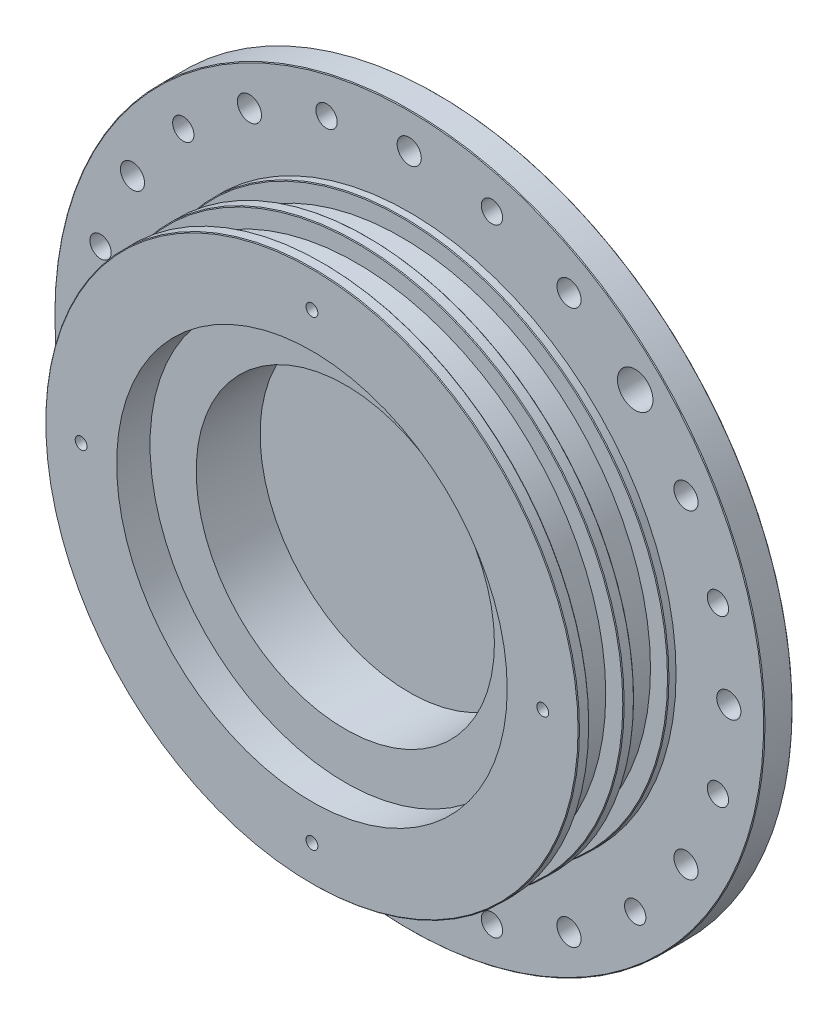
SolidWorks part; units mm, degrees
other "Marquage1"
sketch "Esquisse22" plane through (-100, 100, -114.225) normal (-0.6969, 0.6451, 0.3132) x (0.5706, 0.7634, -0.3027)
sketch "Esquisse26" plane through (-110, 110, -114.225) normal (-0.6969, 0.6451, 0.3132) x (0.5706, 0.7634, -0.3027)
sketch "Esquisse28" plane through (-110, 110, -114.225) normal (-0.6969, 0.6451, 0.3132) x (0.5706, 0.7634, -0.3027)
sketch "Esquisse31" plane through (-110, 110, -114.225) normal (-0.6969, 0.6451, 0.3132) x (0.5706, 0.7634, -0.3027)
sketch "Esquisse32" plane through (-100, 100, -114.225) normal (-0.6969, 0.6451, 0.3132) x (0.5706, 0.7634, -0.3027)
material "AISI 316 Barre d'acier inoxydable recuit (SS)"
ref_plane "Plan de face" through (0, 0, 0) normal (0, 0, 1) x (1, 0, 0)
ref_plane "Plan de dessus" through (0, 0, 0) normal (0, 1, 0) x (1, 0, 0)
ref_plane "Plan de droite" through (0, 0, 0) normal (1, 0, 0) x (0, 0, -1)
sketch "Esquisse1" plane through (0, 0, 0) normal (0, 1, 0) x (1, 0, 0)
  line L0 (87.5, 35.4) -> (0, 35.4)
  line L1 (0, 35.4) -> (0, 0)
  line L2 (0, 0) -> (75.15, 0)
  line L3 (75.15, 0) -> (75.15, 3)
  line L4 (75.15, 3) -> (70.15, 3)
  line L5 (70.15, 3) -> (70.15, 12.6)
  line L6 (70.15, 12.6) -> (75.15, 12.6)
  line L7 (75.15, 12.6) -> (75.15, 15.6)
  line L8 (75.15, 15.6) -> (70.15, 15.6)
  line L9 (70.15, 15.6) -> (70.15, 25.2)
  line L10 (70.15, 25.2) -> (75.15, 25.2)
  line L11 (75.15, 25.2) -> (75.15, 27.4)
  line L12 (75.15, 27.4) -> (87.5, 27.4)
  line L13 (87.5, 27.4) -> (87.5, 35.4)
  line L14 (0, 35.4) -> (0, 0) construction
  point P14 (-21.1135, 134.6836)
  point P15 (0, 0)
  dimension "D1" = 8
  dimension "D2" = 2.2
  dimension "D3" = 9.6
  dimension "D4" = 3
  dimension "D5" = 9.6
  dimension "D6" = 3
  dimension "D7" = 5
  dimension "D8" = 75.15
  dimension "D9" = 87.5
revolve "Révolution1" add sketch "Esquisse1" angle 360 about L14 reverse direction yes
hole_wizard "Diamètre du perçage Ø9.0 (9)1" positions "Esquisse3" profile "Esquisse2" hole size "Ø9.0" standard "Ansi Metric"
sketch "Esquisse3" plane through (0, 0, -27.4) normal (0, 0, 1) x (1, 0, 0)
  point P0 (-87.5, 0)
  point P1 (0, 87.5)
  point P2 (0, -87.5)
  point P3 (87.5, 0)
sketch "Esquisse2" plane through (-87.5, 0, -27.4) normal (1, 0, 0) x (0, -1, 0)
  line L0 (0, 0) -> (0, 3)
  line L1 (0, 3) -> (4.5, 3)
  line L2 (4.5, 3) -> (4.5, 0)
  line L5 (4.5, 0) -> (0, 0)
  line L10 (0, 3) -> (-4.5, 3) construction
  line L11 (0, -6.35) -> (0, 107.95) construction
  dimension "Diamètre du perçage" = 9
  dimension "Profondeur du perçage" = 3
  dimension "Angle de pointe" = 180
hole_wizard "Dégagement M31" positions "Esquisse5" profile "Esquisse4" hole size "M3" standard "Ansi Metric"
sketch "Esquisse5" plane through (0, 0, 0) normal (0, 0, 1) x (1, 0, 0)
  point P0 (-65, 0)
  point P1 (65, 0)
  point P2 (0, 65)
  point P3 (0, -65)
sketch "Esquisse4" plane through (-65, 0, 0) normal (1, 0, 0) x (0, -1, 0)
  line L0 (0, 0) -> (0, 17.001)
  line L1 (0, 17.001) -> (1.666, 16)
  line L2 (1.666, 16) -> (1.666, 0)
  line L5 (1.666, 0) -> (0, 0)
  line L10 (0, 17.001) -> (-1.666, 16) construction
  line L11 (0, -6.35) -> (0, 107.95) construction
  dimension "Diamètre du perçage" = 3.332
  dimension "Profondeur du perçage" = 16
  dimension "Angle de pointe" = 118
hole_wizard "Dégagement M1001" positions "Esquisse7" profile "Esquisse6" hole size "M100" standard "Ansi Metric"
sketch "Esquisse7" plane through (0, 0, 0) normal (0, 0, 1) x (1, 0, 0)
  point P0 (0, 0)
sketch "Esquisse6" plane through (0, 0, 0) normal (1, 0, 0) x (0, -1, 0)
  line L0 (0, 0) -> (0, 27.4)
  line L1 (0, 27.4) -> (55, 27.4)
  line L2 (55, 27.4) -> (55, 0)
  line L5 (55, 0) -> (0, 0)
  line L10 (0, 27.4) -> (-55, 27.4) construction
  line L11 (0, -6.35) -> (0, 107.95) construction
  dimension "Diamètre du perçage" = 110
  dimension "Profondeur du perçage" = 27.4
  dimension "Angle de pointe" = 180
sketch "Esquisse8" plane through (0, 0, -35.4) normal (0, 0, -1) x (-1, 0, 0)
  line L0 (0, 0) -> (0, -108.9201) construction
  circle A0 centre (0, 0) radius 108.9201 construction
  circle A1 centre (0, 0) radius 100
  circle A2 centre (0, 0) radius 77.5
  circle A3 centre (0, 0) radius 87.5 construction
  dimension "D2" = 10
  dimension "D1" = 200
extrude "Boss.-Extru.1" add sketch "Esquisse8" against normal blind 8
ref_plane "Plan1" through (0, -100, 0) normal (0, -1, 0) x (-1, 0, 0)
sketch "Esquisse9" plane through (0, 0, -35.4) normal (0, 0, 1) x (1, 0, 0)
  line L0 (0, -50) -> (0, 0) construction
  circle A0 centre (0, -50) radius 3.4
  circle A17 centre (0, -90) radius 3.4
  circle A18 centre (-25, -43.3013) radius 3.4
  circle A19 centre (-45, -77.9423) radius 3.4
  circle A20 centre (-43.3013, -25) radius 3.4
  circle A21 centre (-77.9423, -45) radius 3.4
  circle A22 centre (-50, 0) radius 3.4
  circle A23 centre (-90, 0) radius 3.4
  circle A24 centre (-43.3013, 25) radius 3.4
  circle A25 centre (-77.9423, 45) radius 3.4
  circle A26 centre (-25, 43.3013) radius 3.4
  circle A27 centre (-45, 77.9423) radius 3.4
  circle A28 centre (0, 50) radius 3.4
  circle A29 centre (0, 90) radius 3.4
  circle A30 centre (25, 43.3013) radius 3.4
  circle A31 centre (45, 77.9423) radius 3.4
  circle A32 centre (43.3013, 25) radius 3.4
  circle A33 centre (77.9423, 45) radius 3.4
  circle A34 centre (50, 0) radius 3.4
  circle A35 centre (90, 0) radius 3.4
  circle A36 centre (43.3013, -25) radius 3.4
  circle A37 centre (77.9423, -45) radius 3.4
  circle A38 centre (25, -43.3013) radius 3.4
  circle A39 centre (45, -77.9423) radius 3.4
  point P6 (15.5142, 43.5591)
  point P8 (0, 0)
  point P17 (0, 0)
  point P28 (0, 0)
  point P31 (0, 0)
  point P55 (0, 0)
  dimension "D1" = 6.8
  dimension "D3" = 90
  dimension "D2" = 50
extrude "Enlèv. mat.-Extru.1" cut sketch "Esquisse9" along normal blind 20
sketch "Esquisse24" plane through (0, 0, -35.4) normal (0, 0, -1) x (-1, 0, 0)
  line L0 (28.0621, 104.7291) -> (0, 0) construction
  line L1 (-54.2118, 93.8976) -> (0, 0) construction
  line L2 (0, 0) -> (0, 90) construction
  line L3 (0, 0) -> (-63.6396, 63.6396) construction
  circle A0 centre (-45, 77.9423) radius 5 construction
  circle A1 centre (23.2937, 86.9333) radius 3
  circle A2 centre (63.6396, 63.6396) radius 3
  circle A3 centre (86.9333, 23.2937) radius 3
  circle A4 centre (86.9333, -23.2937) radius 3
  circle A5 centre (-14, 24.2487) radius 5
  circle A6 centre (7.2469, 27.0459) radius 5
  circle A7 centre (24.2487, 14) radius 5
  circle A8 centre (27.0459, -7.2469) radius 5
  circle A9 centre (14, -24.2487) radius 5
  circle A10 centre (-7.2469, -27.0459) radius 5
  circle A11 centre (-24.2487, -14) radius 5
  circle A12 centre (-27.0459, 7.2469) radius 5
  circle A13 centre (-63.6396, 63.6396) radius 5
  circle A14 centre (63.6396, -63.6396) radius 3
  circle A15 centre (23.2937, -86.9333) radius 3
  circle A16 centre (-23.2937, -86.9333) radius 3
  circle A17 centre (-63.6396, -63.6396) radius 3
  circle A18 centre (-86.9333, -23.2937) radius 3
  circle A19 centre (-86.9333, 23.2937) radius 3
  circle A20 centre (-63.6396, 63.6396) radius 3 construction
  circle A21 centre (-23.2937, 86.9333) radius 3
  point P5 (0, 90)
  point P11 (0, 0)
  point P19 (0, 0)
  point P36 (0, 0)
  dimension "D1" = 6
  dimension "D3" = 10
  dimension "D6" = 10
  dimension "D11" = 15
  dimension "D12" = 10
  dimension "D2" = 90
  dimension "D4" = 90
  dimension "D7" = 28
  dimension "D9" = 45
  dimension "D10" = 15
  dimension "D13" = 90
  dimension "D5" = 12
  dimension "D8" = 8
extrude "Enlèv. mat.-Extru.15" cut sketch "Esquisse24" against normal through all and the other way through all
chamfer "Chanfrein1" distance 0.2 angle 45 7 edges at (75.15, 0, -25.2) (75.15, 0, -3) (75.15, 0, -12.6) (75.15, 0, -15.6) (-100, 0, -35.4) (-100, 0, -27.4) (75.15, 0, 0)
sketch "Esquisse25" plane through (0, 0, -35.4) normal (0, 0, -1) x (-1, 0, 0)
  line L0 (-24.9287, -1.7061) -> (-33.3561, 0.552) construction
  line L1 (-33.3561, 0.552) -> (-29.1632, 16.2) construction
  line L2 (-29.1632, 16.2) -> (-20.7358, 13.9419) construction
  line L3 (-20.7358, 13.9419) -> (-24.9287, -1.7061) construction
  line L4 (0, 0) -> (-31.2596, 8.376) construction
  line L5 (-27.0459, 7.2469) -> (-33.914, -18.3852) construction
  line L6 (-22.5347, 14.4239) -> (-27.3643, 15.718)
  line L7 (-26.7275, -1.2241) -> (-31.5572, 0.07)
  line L8 (-5.7352, 26.1336) -> (-8.2352, 30.4638)
  line L9 (-19.7648, 18.0336) -> (-22.2648, 22.3638)
  line L10 (14.4239, 22.5347) -> (15.718, 27.3643)
  line L11 (-1.2241, 26.7275) -> (0.07, 31.5572)
  line L12 (26.1336, 5.7352) -> (30.4638, 8.2352)
  line L13 (18.0336, 19.7648) -> (22.3638, 22.2648)
  line L14 (22.5347, -14.4239) -> (27.3643, -15.718)
  line L15 (26.7275, 1.2241) -> (31.5572, -0.07)
  line L16 (5.7352, -26.1336) -> (8.2352, -30.4638)
  line L17 (19.7648, -18.0336) -> (22.2648, -22.3638)
  line L18 (-14.4239, -22.5347) -> (-15.718, -27.3643)
  line L19 (1.2241, -26.7275) -> (-0.07, -31.5572)
  line L20 (-26.1336, -5.7352) -> (-30.4638, -8.2352)
  line L21 (-18.0336, -19.7648) -> (-22.3638, -22.2648)
  arc A2 (-33.3561, 0.552) -> (-29.1632, 16.2) centre (-27.0459, 7.2469) cw construction
  arc A3 (-24.9287, -1.7061) -> (-20.7358, 13.9419) centre (-27.0459, 7.2469) ccw construction
  arc A4 (-22.8033, -0.9164) -> (-19.29, 12.1953) centre (-27.0459, 7.2469) ccw
  arc A5 (-19.29, 12.1953) -> (-19.4952, 12.5745) centre (-16.7609, 13.8089) cw
  arc A6 (-19.4952, 12.5745) -> (-21.9939, 14.3309) centre (-22.2295, 11.3402) ccw
  arc A7 (-21.9939, 14.3309) -> (-22.5347, 14.4239) centre (-21.7582, 17.3217) cw
  arc A8 (-27.8791, 15.9079) -> (-27.3643, 15.718) centre (-26.5878, 18.6158) ccw
  arc A9 (-30.9212, 15.6361) -> (-27.8791, 15.9079) centre (-29.1704, 13.2) cw
  arc A10 (-31.2885, 15.4103) -> (-30.9212, 15.6361) centre (-32.672, 18.0722) ccw
  arc A11 (-34.8018, 2.2986) -> (-31.2885, 15.4103) centre (-27.0459, 7.2469) cw
  arc A12 (-34.8018, 2.2986) -> (-34.5966, 1.9193) centre (-37.3309, 0.685) cw
  arc A13 (-34.5966, 1.9193) -> (-32.098, 0.1629) centre (-31.8623, 3.1537) ccw
  arc A14 (-32.098, 0.1629) -> (-31.5572, 0.07) centre (-32.3336, -2.8278) cw
  arc A15 (-26.2127, -1.414) -> (-26.7275, -1.2241) centre (-27.504, -4.1219) ccw
  arc A16 (-23.1707, -1.1423) -> (-26.2127, -1.414) centre (-24.9215, 1.2939) cw
  arc A17 (-22.8033, -0.9164) -> (-23.1707, -1.1423) centre (-21.4198, -3.5784) ccw
  arc A19 (-22.9833, 26.2339) -> (-11.2276, 33.0211) centre (-14, 24.2487) cw
  arc A20 (-11.2276, 33.0211) -> (-10.8082, 32.921) centre (-10.3236, 35.8816) ccw
  arc A21 (-10.8082, 32.921) -> (-8.4649, 30.9621) centre (-11.2928, 29.9604) cw
  arc A22 (-8.4649, 30.9621) -> (-8.2352, 30.4638) centre (-5.6371, 31.9638) ccw
  arc A23 (-5.4185, 25.6855) -> (-5.7352, 26.1336) centre (-3.1371, 27.6336) cw
  arc A24 (-4.8937, 22.6768) -> (-5.4185, 25.6855) centre (-7.6999, 23.7374) ccw
  arc A25 (-5.0167, 22.2635) -> (-4.8937, 22.6768) centre (-2.0874, 21.6161) cw
  arc A26 (-16.7724, 15.4764) -> (-5.0167, 22.2635) centre (-14, 24.2487) ccw
  arc A27 (-16.7724, 15.4764) -> (-17.1918, 15.5764) centre (-17.6764, 12.6158) ccw
  arc A28 (-17.1918, 15.5764) -> (-19.5351, 17.5353) centre (-16.7072, 18.537) cw
  arc A29 (-19.5351, 17.5353) -> (-19.7648, 18.0336) centre (-22.3629, 16.5336) ccw
  arc A30 (-22.5815, 22.8119) -> (-22.2648, 22.3638) centre (-24.8629, 20.8638) cw
  arc A31 (-23.1063, 25.8207) -> (-22.5815, 22.8119) centre (-20.3001, 24.76) ccw
  arc A32 (-22.9833, 26.2339) -> (-23.1063, 25.8207) centre (-25.9126, 26.8813) cw
  arc A33 (2.2986, 34.8018) -> (15.4103, 31.2885) centre (7.2469, 27.0459) cw
  arc A34 (15.4103, 31.2885) -> (15.6361, 30.9212) centre (18.0722, 32.672) ccw
  arc A35 (15.6361, 30.9212) -> (15.9079, 27.8791) centre (13.2, 29.1704) cw
  arc A36 (15.9079, 27.8791) -> (15.718, 27.3643) centre (18.6158, 26.5878) ccw
  arc A37 (14.3309, 21.9939) -> (14.4239, 22.5347) centre (17.3217, 21.7582) cw
  arc A38 (12.5745, 19.4952) -> (14.3309, 21.9939) centre (11.3402, 22.2295) ccw
  arc A39 (12.1953, 19.29) -> (12.5745, 19.4952) centre (13.8089, 16.7609) cw
  arc A40 (-0.9164, 22.8033) -> (12.1953, 19.29) centre (7.2469, 27.0459) ccw
  arc A41 (-0.9164, 22.8033) -> (-1.1423, 23.1707) centre (-3.5784, 21.4198) ccw
  arc A42 (-1.1423, 23.1707) -> (-1.414, 26.2127) centre (1.2939, 24.9215) cw
  arc A43 (-1.414, 26.2127) -> (-1.2241, 26.7275) centre (-4.1219, 27.504) ccw
  arc A44 (0.1629, 32.098) -> (0.07, 31.5572) centre (-2.8278, 32.3336) cw
  arc A45 (1.9193, 34.5966) -> (0.1629, 32.098) centre (3.1537, 31.8623) ccw
  arc A46 (2.2986, 34.8018) -> (1.9193, 34.5966) centre (0.685, 37.3309) cw
  arc A47 (26.2339, 22.9833) -> (33.0211, 11.2276) centre (24.2487, 14) cw
  arc A48 (33.0211, 11.2276) -> (32.921, 10.8082) centre (35.8816, 10.3236) ccw
  arc A49 (32.921, 10.8082) -> (30.9621, 8.4649) centre (29.9604, 11.2928) cw
  arc A50 (30.9621, 8.4649) -> (30.4638, 8.2352) centre (31.9638, 5.6371) ccw
  arc A51 (25.6855, 5.4185) -> (26.1336, 5.7352) centre (27.6336, 3.1371) cw
  arc A52 (22.6768, 4.8937) -> (25.6855, 5.4185) centre (23.7374, 7.6999) ccw
  arc A53 (22.2635, 5.0167) -> (22.6768, 4.8937) centre (21.6161, 2.0874) cw
  arc A54 (15.4764, 16.7724) -> (22.2635, 5.0167) centre (24.2487, 14) ccw
  arc A55 (15.4764, 16.7724) -> (15.5764, 17.1918) centre (12.6158, 17.6764) ccw
  arc A56 (15.5764, 17.1918) -> (17.5353, 19.5351) centre (18.537, 16.7072) cw
  arc A57 (17.5353, 19.5351) -> (18.0336, 19.7648) centre (16.5336, 22.3629) ccw
  arc A58 (22.8119, 22.5815) -> (22.3638, 22.2648) centre (20.8638, 24.8629) cw
  arc A59 (25.8207, 23.1063) -> (22.8119, 22.5815) centre (24.76, 20.3001) ccw
  arc A60 (26.2339, 22.9833) -> (25.8207, 23.1063) centre (26.8813, 25.9126) cw
  arc A61 (34.8018, -2.2986) -> (31.2885, -15.4103) centre (27.0459, -7.2469) cw
  arc A62 (31.2885, -15.4103) -> (30.9212, -15.6361) centre (32.672, -18.0722) ccw
  arc A63 (30.9212, -15.6361) -> (27.8791, -15.9079) centre (29.1704, -13.2) cw
  arc A64 (27.8791, -15.9079) -> (27.3643, -15.718) centre (26.5878, -18.6158) ccw
  arc A65 (21.9939, -14.3309) -> (22.5347, -14.4239) centre (21.7582, -17.3217) cw
  arc A66 (19.4952, -12.5745) -> (21.9939, -14.3309) centre (22.2295, -11.3402) ccw
  arc A67 (19.29, -12.1953) -> (19.4952, -12.5745) centre (16.7609, -13.8089) cw
  arc A68 (22.8033, 0.9164) -> (19.29, -12.1953) centre (27.0459, -7.2469) ccw
  arc A69 (22.8033, 0.9164) -> (23.1707, 1.1423) centre (21.4198, 3.5784) ccw
  arc A70 (23.1707, 1.1423) -> (26.2127, 1.414) centre (24.9215, -1.2939) cw
  arc A71 (26.2127, 1.414) -> (26.7275, 1.2241) centre (27.504, 4.1219) ccw
  arc A72 (32.098, -0.1629) -> (31.5572, -0.07) centre (32.3336, 2.8278) cw
  arc A73 (34.5966, -1.9193) -> (32.098, -0.1629) centre (31.8623, -3.1537) ccw
  arc A74 (34.8018, -2.2986) -> (34.5966, -1.9193) centre (37.3309, -0.685) cw
  arc A75 (22.9833, -26.2339) -> (11.2276, -33.0211) centre (14, -24.2487) cw
  arc A76 (11.2276, -33.0211) -> (10.8082, -32.921) centre (10.3236, -35.8816) ccw
  arc A77 (10.8082, -32.921) -> (8.4649, -30.9621) centre (11.2928, -29.9604) cw
  arc A78 (8.4649, -30.9621) -> (8.2352, -30.4638) centre (5.6371, -31.9638) ccw
  arc A79 (5.4185, -25.6855) -> (5.7352, -26.1336) centre (3.1371, -27.6336) cw
  arc A80 (4.8937, -22.6768) -> (5.4185, -25.6855) centre (7.6999, -23.7374) ccw
  arc A81 (5.0167, -22.2635) -> (4.8937, -22.6768) centre (2.0874, -21.6161) cw
  arc A82 (16.7724, -15.4764) -> (5.0167, -22.2635) centre (14, -24.2487) ccw
  arc A83 (16.7724, -15.4764) -> (17.1918, -15.5764) centre (17.6764, -12.6158) ccw
  arc A84 (17.1918, -15.5764) -> (19.5351, -17.5353) centre (16.7072, -18.537) cw
  arc A85 (19.5351, -17.5353) -> (19.7648, -18.0336) centre (22.3629, -16.5336) ccw
  arc A86 (22.5815, -22.8119) -> (22.2648, -22.3638) centre (24.8629, -20.8638) cw
  arc A87 (23.1063, -25.8207) -> (22.5815, -22.8119) centre (20.3001, -24.76) ccw
  arc A88 (22.9833, -26.2339) -> (23.1063, -25.8207) centre (25.9126, -26.8813) cw
  arc A89 (-2.2986, -34.8018) -> (-15.4103, -31.2885) centre (-7.2469, -27.0459) cw
  arc A90 (-15.4103, -31.2885) -> (-15.6361, -30.9212) centre (-18.0722, -32.672) ccw
  arc A91 (-15.6361, -30.9212) -> (-15.9079, -27.8791) centre (-13.2, -29.1704) cw
  arc A92 (-15.9079, -27.8791) -> (-15.718, -27.3643) centre (-18.6158, -26.5878) ccw
  arc A93 (-14.3309, -21.9939) -> (-14.4239, -22.5347) centre (-17.3217, -21.7582) cw
  arc A94 (-12.5745, -19.4952) -> (-14.3309, -21.9939) centre (-11.3402, -22.2295) ccw
  arc A95 (-12.1953, -19.29) -> (-12.5745, -19.4952) centre (-13.8089, -16.7609) cw
  arc A96 (0.9164, -22.8033) -> (-12.1953, -19.29) centre (-7.2469, -27.0459) ccw
  arc A97 (0.9164, -22.8033) -> (1.1423, -23.1707) centre (3.5784, -21.4198) ccw
  arc A98 (1.1423, -23.1707) -> (1.414, -26.2127) centre (-1.2939, -24.9215) cw
  arc A99 (1.414, -26.2127) -> (1.2241, -26.7275) centre (4.1219, -27.504) ccw
  arc A100 (-0.1629, -32.098) -> (-0.07, -31.5572) centre (2.8278, -32.3336) cw
  arc A101 (-1.9193, -34.5966) -> (-0.1629, -32.098) centre (-3.1537, -31.8623) ccw
  arc A102 (-2.2986, -34.8018) -> (-1.9193, -34.5966) centre (-0.685, -37.3309) cw
  arc A103 (-26.2339, -22.9833) -> (-33.0211, -11.2276) centre (-24.2487, -14) cw
  arc A104 (-33.0211, -11.2276) -> (-32.921, -10.8082) centre (-35.8816, -10.3236) ccw
  arc A105 (-32.921, -10.8082) -> (-30.9621, -8.4649) centre (-29.9604, -11.2928) cw
  arc A106 (-30.9621, -8.4649) -> (-30.4638, -8.2352) centre (-31.9638, -5.6371) ccw
  arc A107 (-25.6855, -5.4185) -> (-26.1336, -5.7352) centre (-27.6336, -3.1371) cw
  arc A108 (-22.6768, -4.8937) -> (-25.6855, -5.4185) centre (-23.7374, -7.6999) ccw
  arc A109 (-22.2635, -5.0167) -> (-22.6768, -4.8937) centre (-21.6161, -2.0874) cw
  arc A110 (-15.4764, -16.7724) -> (-22.2635, -5.0167) centre (-24.2487, -14) ccw
  arc A111 (-15.4764, -16.7724) -> (-15.5764, -17.1918) centre (-12.6158, -17.6764) ccw
  arc A112 (-15.5764, -17.1918) -> (-17.5353, -19.5351) centre (-18.537, -16.7072) cw
  arc A113 (-17.5353, -19.5351) -> (-18.0336, -19.7648) centre (-16.5336, -22.3629) ccw
  arc A114 (-22.8119, -22.5815) -> (-22.3638, -22.2648) centre (-20.8638, -24.8629) cw
  arc A115 (-25.8207, -23.1063) -> (-22.8119, -22.5815) centre (-24.76, -20.3001) ccw
  arc A116 (-26.2339, -22.9833) -> (-25.8207, -23.1063) centre (-26.8813, -25.9126) cw
  point P7 (-22.8322, 6.1179)
  point P10 (0, 0)
  point P35 (-24.9495, 15.0709)
  point P250 (0, 0)
  dimension "D1" = 9.2
  dimension "D3" = 3
  dimension "D4" = 2.5
  dimension "D2" = 16.2
  dimension "D5" = 8
extrude "Enlèv. mat.-Extru.18" cut sketch "Esquisse25" against normal blind 2
sketch "Esquisse35" plane through (0, 0, -27.4) normal (0, 0, 1) x (1, 0, 0)
  circle A0 centre (0, 0) radius 55
  circle A1 centre (0, 0) radius 42
  circle A4 centre (0, 0) radius 55 construction
  dimension "D1" = 84
extrude "Boss.-Extru.4" add sketch "Esquisse35" along normal blind 18
sketch "Esquisse36" plane through (0, 0, -27.4) normal (0, 0, 1) x (1, 0, 0)
  circle A0 centre (-27.0459, -7.2469) radius 5
  circle A1 centre (-27.0459, -7.2469) radius 5 construction
  circle A2 centre (-24.2487, 14) radius 5
  circle A3 centre (-7.2469, 27.0459) radius 5
  circle A4 centre (14, 24.2487) radius 5
  circle A5 centre (27.0459, 7.2469) radius 5
  circle A6 centre (24.2487, -14) radius 5
  circle A7 centre (7.2469, -27.0459) radius 5
  circle A8 centre (-14, -24.2487) radius 5
  point P14 (0, 0)
  dimension "D1" = 8
extrude "Boss.-Extru.5" add sketch "Esquisse36" against normal blind 4
extrude "Enlèv. mat.-Extru.20" cut sketch "Esquisse9<2>" along normal blind 20
sketch "Esquisse9<2>" plane through (0, 0, -35.4) normal (0, 0, 1) x (1, 0, 0) same geometry as "Esquisse9"
equation "\"_à\"=76.5769"
